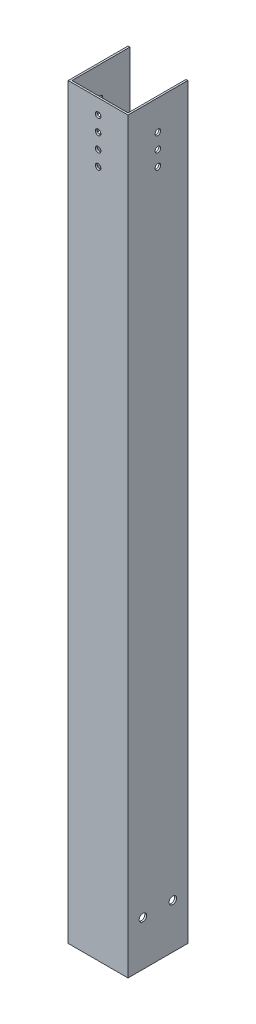
SolidWorks part; units mm, degrees
ref_plane "Front Plane" through (0, 0, 0) normal (0, 0, 1) x (1, 0, 0)
ref_plane "Top Plane" through (0, 0, 0) normal (0, 1, 0) x (1, 0, 0)
ref_plane "Right Plane" through (0, 0, 0) normal (1, 0, 0) x (0, 0, -1)
sketch "Sketch1" plane through (0, 0, 0) normal (0, 1, 0) x (1, 0, 0)
  line L0 (0, 0) -> (50.8, 0)
  line L1 (50.8, 0) -> (50.8, 50.8)
  line L2 (50.8, 50.8) -> (49.2125, 50.8)
  line L3 (49.2125, 50.8) -> (49.2125, 1.5875)
  line L4 (49.2125, 1.5875) -> (1.5875, 1.5875)
  line L5 (1.5875, 1.5875) -> (1.5875, 50.8)
  line L6 (1.5875, 50.8) -> (0, 50.8)
  line L7 (0, 50.8) -> (0, 0)
  dimension "D1" = 50.8
  dimension "D2" = 50.8
  dimension "D3" = 1.5875
  dimension "D4" = 1.5875
  dimension "D5" = 1.5875
extrude "Boss-Extrude1" add sketch "Sketch1" along normal blind 635
sketch "Sketch2" plane through (50.8, 0, 0) normal (1, 0, 0) x (0, 0, -1)
  line L0 (0, 635) -> (0, 0) construction
  line L1 (0, 0) -> (50.8, 0) construction
  line L2 (0, 635) -> (50.8, 635) construction
  line L4 (50.8, 635) -> (50.8, 0) construction
  circle A0 centre (12.7, 38.1) radius 3.175
  circle A1 centre (38.1, 38.1) radius 3.175
  circle A2 centre (25.4, 609.6) radius 2.3813
  circle A3 centre (25.4, 596.9) radius 2.3813
  circle A4 centre (25.4, 584.2) radius 2.3813
  point P14 (23.3691, 615.6286)
  point P15 (24.5479, 600.3044)
  dimension "D1" = 6.35
  dimension "D2" = 25.4
  dimension "D3" = 12.7
  dimension "D4" = 38.1
  dimension "D5" = 4.7625
  dimension "D6" = 12.7
  dimension "D7" = 12.7
  dimension "D8" = 25.4
  dimension "D9" = 25.4
extrude "Cut-Extrude1" cut sketch "Sketch2" against normal through all
sketch "Sketch3" plane through (0, 0, 0) normal (0, 0, 1) x (1, 0, 0)
  line L0 (0, 635) -> (50.8, 635) construction
  line L1 (50.8, 635) -> (50.8, 0) construction
  circle A0 centre (25.4, 622.3) radius 2.3813
  circle A1 centre (25.4, 609.6) radius 2.3813
  circle A2 centre (25.4, 596.9) radius 2.3813
  circle A3 centre (25.4, 584.2) radius 2.3813
  point P8 (0, 0)
  point P9 (24.0122, 599.7964)
  point P10 (24.0122, 588.3271)
  point P11 (24.0122, 576.6904)
  dimension "D1" = 4.7625
  dimension "D2" = 12.7
  dimension "D3" = 12.7
  dimension "D4" = 12.7
  dimension "D5" = 12.7
  dimension "D6" = 25.4
extrude "Cut-Extrude2" cut sketch "Sketch3" against normal through all
